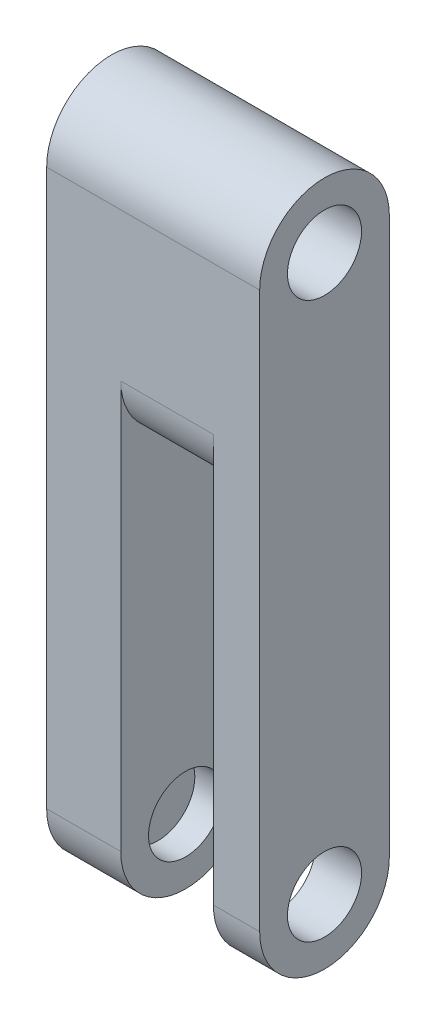
SolidWorks part; units mm, degrees
material "ABS"
ref_plane "Спереди" through (0, 0, 0) normal (0, 0, 1) x (1, 0, 0)
ref_plane "Сверху" through (0, 0, 0) normal (0, 1, 0) x (1, 0, 0)
ref_plane "Справа" through (0, 0, 0) normal (1, 0, 0) x (0, 0, -1)
sketch "Эскиз1" plane through (0, 0, 0) normal (1, 0, 0) x (0, 0, -1)
  line L0 (3.5, 30) -> (3.5, -49970) construction
  line L2 (0, 0) -> (0, 30)
  line L4 (7, 0) -> (7, 30)
  line L5 (0, 0) -> (7, 30) construction
  line L6 (0, 30) -> (7, 0) construction
  line L7 (3.5, 15) -> (50003.5, 15) construction
  circle A0 centre (3.5, 30) radius 2
  arc A1 (0, 30) -> (7, 30) centre (3.5, 30) cw
  circle A2 centre (3.5, 0) radius 2
  arc A3 (0, 0) -> (7, 0) centre (3.5, 0) ccw
  point P4 (3.5, 15)
  dimension "D3" = 4
  dimension "D4" = 3.5
  dimension "D1" = 30
  dimension "D2" = 7
  dimension "D5" = 30
extrude "Бобышка-Вытянуть1" add sketch "Эскиз1" along normal blind 11.5 contours L2 A1 L4 A3
sketch "Эскиз2" plane through (11.5, 0, 0) normal (1, 0, 0) x (0, 0, -1)
  line L0 (0, 11.9718) -> (0, 50011.9718) construction
  line L2 (7, 19.5747) -> (7, -49980.4253) construction
  line L4 (3.5, 33.5) -> (3.5, -49966.5) construction
  line L5 (0, 0) -> (50000, 0) construction
  line L6 (0, 30) -> (50000, 30) construction
  line L7 (-2.9994, 15) -> (49997.0006, 15) construction
  arc A0 (7, 30) -> (0, 30) centre (3.5, 30) ccw construction
  arc A1 (0, 0) -> (7, 0) centre (3.5, 0) ccw construction
  circle A2 centre (3.5, 30) radius 2
  circle A3 centre (3.5, 0) radius 2
  point P9 (3.5, 33.5)
  point P13 (3.5, -3.5)
  point P22 (3.5, 30)
  dimension "D3" = 4
  dimension "D1" = 30
  dimension "D2" = 15
extrude "Вырез-Вытянуть2" cut sketch "Эскиз2" against normal blind 9
ref_plane "Плоскость1" through (4, 0, 0) normal (1, 0, 0) x (0, 0, -1)
sketch "Эскиз3" plane through (4, 0, 0) normal (1, 0, 0) x (0, 0, -1)
  line L0 (0, 0) -> (50000, 0) construction
  line L1 (-996.5, 30) -> (49003.5, 30) construction
  line L3 (-1005.198, 22) -> (48994.802, 22) construction
  line L4 (-14.8525, 26) -> (12.3896, 26) construction
  line L7 (0, 22) -> (-5.9735, 22)
  line L8 (-5.9735, 22) -> (-5.9735, -6.2075)
  line L9 (-5.9735, -6.2075) -> (11.9268, -6.2075)
  line L10 (11.9268, -6.2075) -> (11.9268, 22)
  line L11 (11.9268, 22) -> (7, 22)
  arc A1 (0, 22) -> (7, 22) centre (3.5, 22) ccw
  dimension "D1" = 8
  dimension "D2" = 4
extrude "Вырез-Вытянуть3" cut sketch "Эскиз3" along normal blind 5
